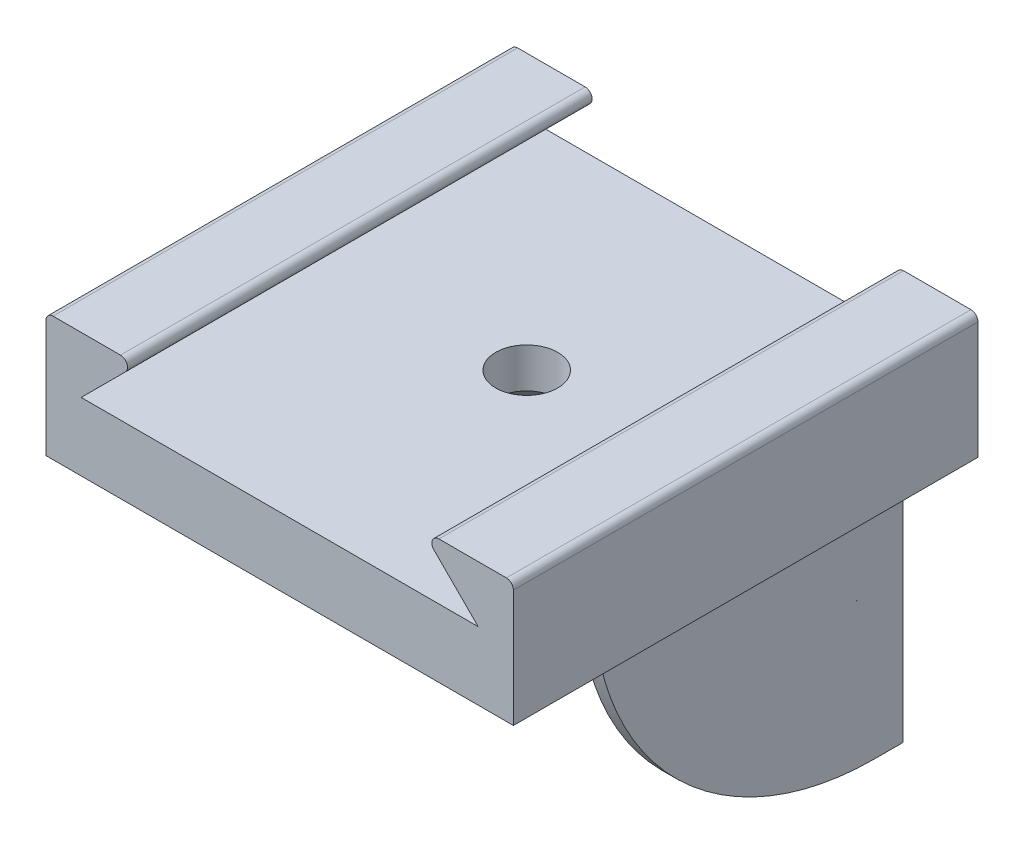
SolidWorks part; units mm, degrees
ref_plane "Спереди" through (0, 0, 0) normal (0, 0, 1) x (1, 0, 0)
ref_plane "Сверху" through (0, 0, 0) normal (0, 1, 0) x (1, 0, 0)
ref_plane "Справа" through (0, 0, 0) normal (1, 0, 0) x (0, 0, -1)
sketch "Эскиз1" plane through (0, 0, 0) normal (0, 0, 1) x (1, 0, 0)
  line L0 (-14.1864, -3.9492) -> (-11.04, -0.8028)
  line L2 (-14.1864, -3.9492) -> (14.0136, -3.9492)
  line L3 (14.0136, -3.9492) -> (10.8671, -0.8028)
  line L4 (-11.3935, 0.0508) -> (-16.1864, 0.0508)
  line L5 (-16.6864, -0.4492) -> (-16.6864, -8.7811)
  line L6 (-16.6864, -8.7811) -> (16.5136, -8.7811)
  line L7 (16.5136, -8.7811) -> (16.5136, -0.4492)
  line L8 (16.0136, 0.0508) -> (11.2207, 0.0508)
  arc A0 (-16.1864, 0.0508) -> (-16.6864, -0.4492) centre (-16.1864, -0.4492) ccw
  arc A1 (16.5136, -0.4492) -> (16.0136, 0.0508) centre (16.0136, -0.4492) ccw
  arc A2 (11.2207, 0.0508) -> (10.8671, -0.8028) centre (11.2207, -0.4492) ccw
  arc A3 (-11.04, -0.8028) -> (-11.3935, 0.0508) centre (-11.3935, -0.4492) ccw
  point P10 (-16.6864, 0.0508)
  point P13 (16.5136, 0.0508)
  point P16 (10.0136, 0.0508)
  point P19 (-10.1864, 0.0508)
  dimension "D6" = 0.5
  dimension "D1" = 45
  dimension "D2" = 45
  dimension "D3" = 6.5
  dimension "D4" = 28.2
  dimension "D5" = 6.5
extrude "Бобышка-Вытянуть1" add sketch "Эскиз1" along normal blind 33
sketch "Эскиз2" plane through (0, -8.7811, 0) normal (0, -1, 0) x (1, 0, 0)
  line L0 (-0.0864, 33) -> (0, 0) construction
  line L1 (-16.6864, 33) -> (16.5136, 33) construction
  line L2 (-16.6864, 0) -> (16.5136, 0) construction
  line L3 (-11.2049, 0) -> (11.1951, 0)
  line L4 (-11.2049, 0) -> (-11.2049, 2)
  line L5 (-10.2049, 2) -> (10.1951, 2)
  line L6 (11.1951, 0) -> (11.1951, 2)
  line L10 (-11.2049, 2) -> (-11.2049, 22)
  line L11 (-11.2049, 22) -> (-10.2049, 22)
  line L12 (-10.2049, 2) -> (-10.2049, 22)
  line L14 (11.1951, 2) -> (11.1951, 22)
  line L15 (11.1951, 22) -> (10.1951, 22)
  line L16 (10.1951, 2) -> (10.1951, 22)
  point P5 (-0.0049, 1.8738)
  dimension "D1" = 22.4
  dimension "D2" = 2
  dimension "D3" = 1
  dimension "D4" = 20
  dimension "D5" = 1
  dimension "D6" = 20
extrude "Бобышка-Вытянуть2" add sketch "Эскиз2" along normal blind 20.2
fillet "Скругление1" radius 20 2 edges at (-10.7049, -28.9811, 22) (10.6951, -28.9811, 22)
fillet "Скругление2" radius 2 2 edges at (-11.2049, -8.7811, 11) (11.1951, -8.7811, 11)
sketch "Эскиз3" plane through (0, 0, 0) normal (0, 0, -1) x (-1, 0, 0)
  line L0 (0.0049, -28.9811) -> (0.0049, -8.7811) construction
  line L1 (11.2049, -28.9811) -> (-11.1951, -28.9811) construction
  line L2 (0.0049, -18.8811) -> (-11.1951, -18.8811) construction
  line L3 (-11.1951, -28.9811) -> (-11.1951, -10.7811) construction
  line L5 (-7.9951, -26.8811) -> (8.0049, -26.8811) construction
  line L6 (-7.9951, -26.8811) -> (-7.9951, -10.8811) construction
  line L7 (-7.9951, -10.8811) -> (8.0049, -10.8811) construction
  line L8 (8.0049, -26.8811) -> (8.0049, -10.8811) construction
  line L9 (-7.9951, -26.8811) -> (8.0049, -10.8811) construction
  line L10 (-7.9951, -10.8811) -> (8.0049, -26.8811) construction
  circle A0 centre (-7.9951, -10.8811) radius 1.1
  circle A1 centre (8.0049, -10.8811) radius 1.1
  circle A2 centre (8.0049, -26.8811) radius 1.1
  circle A3 centre (-7.9951, -26.8811) radius 1.1
  circle A4 centre (0.0049, -18.8811) radius 8
  dimension "D1" = 16
  dimension "D2" = 16
extrude "Вырез-Вытянуть1" cut sketch "Эскиз3" against normal up to next
fillet "Скругление3" radius 0.5 5 edges at (10.1951, -18.8811, 2) (-10.2049, -18.8811, 2) (-0.0049, -8.7811, 2) (10.1951, -8.7811, 12) (-10.2049, -8.7811, 12)
sketch "Эскиз4" plane through (0, -3.9492, 0) normal (0, 1, 0) x (1, 0, 0)
  line L0 (0, 0) -> (-0.0864, -33) construction
  line L1 (14.0136, -33) -> (-14.1864, -33) construction
  line L2 (14.0136, 0) -> (-14.1864, 0) construction
  circle A0 centre (-0.0406, -15.5) radius 2.2
  point P7 (0, 0)
  dimension "D1" = 15.5
extrude "Вырез-Вытянуть2" cut sketch "Эскиз4" against normal up to next
chamfer "Фаска1" distance 2 angle 45 1 edges at (-0.0406, -8.7811, 17.7)
